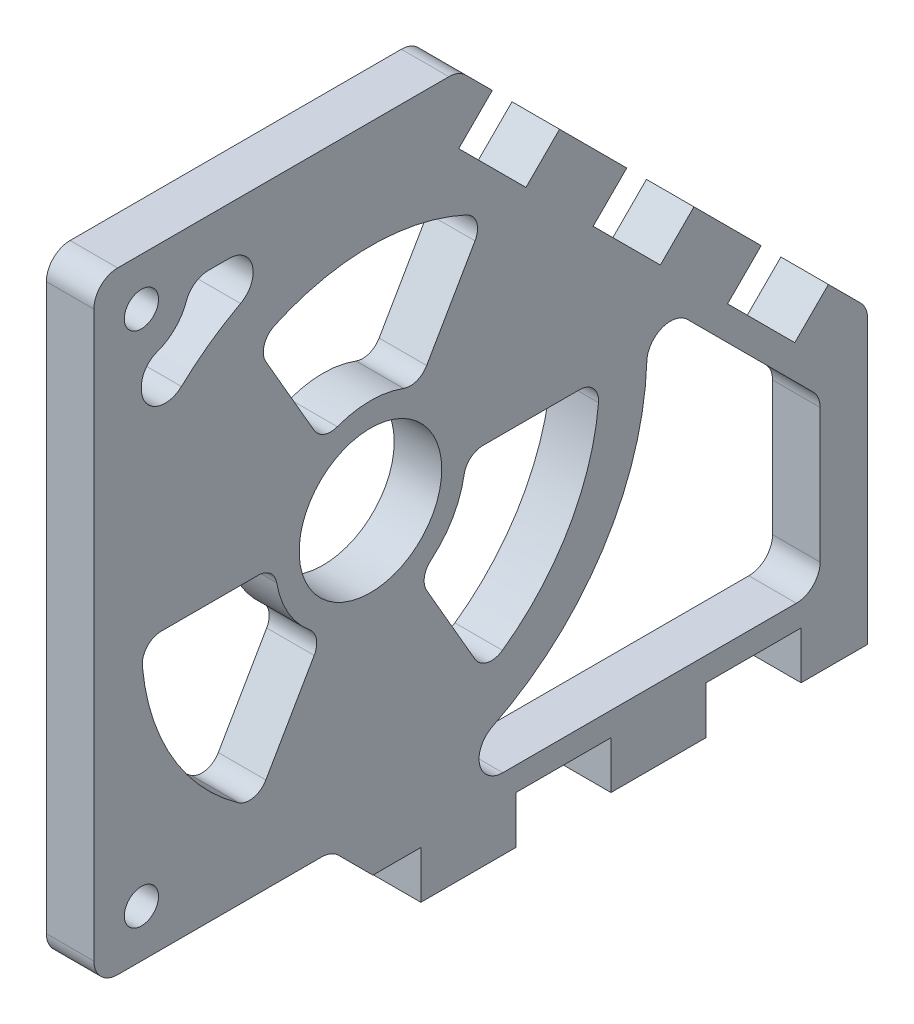
SolidWorks part; units mm, degrees
material "Custom Plastic"
ref_plane "Front Plane" through (0, 0, 0) normal (0, 0, 1) x (1, 0, 0)
ref_plane "Top Plane" through (0, 0, 0) normal (0, 1, 0) x (1, 0, 0)
ref_plane "Right Plane" through (0, 0, 0) normal (1, 0, 0) x (0, 0, -1)
sketch "Sketch2" plane through (0, 0, 0) normal (1, 0, 0) x (0, 0, -1)
  line L0 (0, 0) -> (0, 26.162) construction
  line L1 (0, 26.162) -> (0, 95.25) construction
  line L2 (-55.118, 95.25) -> (0, 95.25) construction
  line L3 (-61.468, 95.25) -> (-61.468, 26.162) construction
  line L4 (-61.468, 26.162) -> (0, 26.162) construction
  line L5 (-45.72, 0) -> (45.72, 0)
  line L6 (-67.818, 101.6) -> (-67.818, 19.812)
  line L7 (45.72, 7.9375) -> (-29.718, 7.9375)
  line L8 (45.72, 0) -> (52.07, 0)
  line L9 (-67.818, 19.812) -> (-45.72, 0)
  line L10 (-55.118, 101.6) -> (-19.0732, 101.6)
  line L11 (-61.468, 95.25) -> (-61.468, 101.6) construction
  line L12 (-61.468, 95.25) -> (-67.818, 95.25) construction
  line L13 (-61.468, 26.162) -> (-67.818, 26.162) construction
  line L14 (-61.468, 26.162) -> (-61.468, 19.812) construction
  line L15 (-55.118, 101.6) -> (-67.818, 101.6)
  line L16 (-61.468, 95.25) -> (-55.118, 95.25) construction
  line L17 (-36.068, 19.812) -> (-29.718, 13.462)
  line L18 (-55.118, 95.25) -> (-55.118, 101.6) construction
  line L19 (-67.818, 19.812) -> (-36.068, 19.812)
  line L20 (-29.718, 13.462) -> (-29.718, 7.9375)
  line L21 (52.07, 0) -> (52.07, 7.9375)
  line L22 (52.07, 7.9375) -> (45.72, 7.9375)
  line L23 (-29.718, 7.9375) -> (-24.1935, 7.9375)
  line L24 (-19.0732, 101.6) -> (52.07, 30.4568)
  line L25 (52.07, 30.4568) -> (52.07, 7.9375)
  circle A0 centre (-61.468, 95.25) radius 2.286
  circle A1 centre (-61.468, 26.162) radius 2.286
  point P0 (0, 0)
  point P1 (-61.468, 95.25)
  point P3 (-61.468, 26.162)
  dimension "D4" = 4.572
  dimension "D7" = 6.35
  dimension "D2" = 26.162
  dimension "D3" = 61.468
  dimension "D5" = 7.9375
  dimension "D6" = 91.44
  dimension "D8" = 6.35
  dimension "D9" = 31.75
  dimension "D10" = 45
  dimension "D11" = 95.25
  dimension "D12" = 6.35
  dimension "D13" = 69.85
extrude "Main" add sketch "Sketch2" along normal blind 6.35 contours L7 A1 A0 | L7 region at (0, 49.7959, 16.6078)
sketch "Sketch5" plane through (6.35, 0, 0) normal (1, 0, 0) x (0, 0, -1)
  line L0 (-36.83, 7.9375) -> (-36.83, 14.2875)
  line L1 (52.07, 7.9375) -> (-29.718, 7.9375) construction
  line L2 (-36.83, 14.2875) -> (-24.13, 14.2875)
  line L3 (-24.13, 14.2875) -> (-24.13, 7.9375)
  line L4 (-24.13, 7.9375) -> (-11.43, 7.9375) construction
  line L5 (-11.43, 7.9375) -> (-11.43, 14.2875)
  line L6 (-11.43, 14.2875) -> (1.27, 14.2875)
  line L7 (1.27, 14.2875) -> (1.27, 7.9375)
  line L8 (1.27, 7.9375) -> (13.97, 7.9375) construction
  line L9 (13.97, 7.9375) -> (13.97, 14.2875)
  line L10 (13.97, 14.2875) -> (26.67, 14.2875)
  line L11 (26.67, 14.2875) -> (26.67, 7.9375)
  line L12 (-19.0732, 101.6) -> (52.07, 30.4568) construction
  line L13 (-36.83, 7.9375) -> (-24.13, 7.9375)
  line L14 (-11.43, 7.9375) -> (1.27, 7.9375)
  line L15 (13.97, 7.9375) -> (26.67, 7.9375)
  line L16 (12.3577, 70.1691) -> (21.338, 61.1888) construction
  line L21 (16.8478, 56.6987) -> (21.338, 61.1888)
  line L22 (25.8281, 47.7185) -> (16.8478, 56.6987)
  line L23 (30.3182, 52.2086) -> (25.8281, 47.7185)
  line L24 (21.338, 61.1888) -> (30.3182, 52.2086)
  line L25 (-1.1127, 74.6592) -> (3.3775, 79.1494)
  line L26 (7.8676, 65.679) -> (-1.1127, 74.6592)
  line L27 (12.3577, 70.1691) -> (7.8676, 65.679)
  line L28 (3.3775, 79.1494) -> (12.3577, 70.1691)
  line L29 (-19.0732, 92.6197) -> (-14.5831, 97.1099)
  line L30 (-10.0929, 83.6395) -> (-19.0732, 92.6197)
  line L31 (-5.6028, 88.1296) -> (-10.0929, 83.6395)
  line L32 (-14.5831, 97.1099) -> (-5.6028, 88.1296)
  line L33 (-5.6028, 88.1296) -> (3.3775, 79.1494) construction
  line L35 (39.37, 7.9375) -> (39.37, 43.1568)
  line L36 (52.07, 7.9375) -> (-29.718, 7.9375) construction
  line L37 (39.37, 43.1568) -> (52.07, 43.1568)
  line L38 (52.07, 43.1568) -> (52.07, 7.9375)
  line L39 (52.07, 7.9375) -> (39.37, 7.9375)
  line L40 (26.67, 7.9375) -> (39.37, 7.9375) construction
  line L41 (52.07, 30.4568) -> (52.07, 7.9375) construction
  dimension "D5" = 6.35
  dimension "D1" = 6.35
  dimension "D2" = 12.7
extrude "Acrylic Joint" cut sketch "Sketch5" against normal through all
sketch "Sketch6" plane through (6.35, 0, 0) normal (1, 0, 0) x (0, 0, -1)
  line L0 (35.56, 7.9375) -> (35.56, 46.9668)
  line L1 (39.37, 7.9375) -> (26.67, 7.9375) construction
  line L2 (35.56, 46.9668) -> (39.37, 46.9668)
  line L3 (39.37, 43.1568) -> (39.37, 7.9375) construction
  line L4 (39.37, 46.9668) -> (39.37, 7.9375)
  line L5 (39.37, 7.9375) -> (35.56, 7.9375)
  line L6 (30.3182, 52.2086) -> (39.37, 43.1568) construction
  dimension "D2" = 3.81
extrude "Cut-Extrude1" cut sketch "Sketch6" against normal through all
fillet "Fillet4" radius 3.175 5 edges at (3.175, 101.6, 67.818) (3.175, 19.812, 67.818) (3.175, 19.812, 36.068) (3.175, 101.6, 19.0732) (3.175, 46.9668, -35.56)
sketch "Sketch7" plane through (6.35, 0, 0) normal (1, 0, 0) x (0, 0, -1)
  line L0 (-61.468, 95.25) -> (-26.1936, 95.25) construction
  line L1 (-26.1936, 95.25) -> (29.21, 39.8464) construction
  line L2 (29.21, 39.8464) -> (29.21, 17.4625) construction
  line L3 (29.21, 17.4625) -> (-24.7382, 17.4625) construction
  line L4 (-24.7382, 17.4625) -> (-33.4377, 26.162) construction
  line L5 (-33.4377, 26.162) -> (-61.468, 26.162) construction
  line L6 (-61.468, 26.162) -> (-61.468, 95.25) construction
  line L7 (-35.1381, 18.8821) -> (-30.5435, 14.2875) construction
  line L8 (-1.1127, 74.6592) -> (7.8676, 65.679) construction
  line L9 (1.27, 14.2875) -> (-11.43, 14.2875) construction
  line L10 (-64.643, 19.812) -> (-37.3831, 19.812) construction
  line L11 (-67.818, 98.425) -> (-67.818, 22.987) construction
  line L12 (-64.643, 101.6) -> (-20.3883, 101.6) construction
  line L13 (-46.1687, 83.1519) -> (-30.8693, 56.6527) construction
  line L14 (-30.8693, 56.6527) -> (-15.57, 83.1519) construction
  line L15 (-30.8693, 56.6527) -> (-0.2706, 56.6527) construction
  line L16 (-30.8693, 56.6527) -> (-15.57, 30.1535) construction
  line L17 (-30.8693, 56.6527) -> (-46.1687, 30.1535) construction
  line L18 (-30.8693, 56.6527) -> (-61.468, 56.6527) construction
  line L19 (-61.468, 56.6527) -> (-46.1687, 83.1519) construction
  line L20 (-46.1687, 83.1519) -> (-15.57, 83.1519) construction
  line L21 (-15.57, 83.1519) -> (-0.2706, 56.6527) construction
  line L22 (-0.2706, 56.6527) -> (-15.57, 30.1535) construction
  line L23 (-15.57, 30.1535) -> (-46.1687, 30.1535) construction
  line L24 (-46.1687, 30.1535) -> (-61.468, 56.6527) construction
  line L25 (35.56, 45.6517) -> (35.56, 7.9375) construction
  line L26 (-46.1687, 83.1519) -> (-37.2193, 67.6512)
  line L27 (-24.5193, 67.6512) -> (-15.57, 83.1519)
  line L28 (-18.1693, 56.6527) -> (-0.2706, 56.6527)
  line L29 (-15.57, 30.1535) -> (-24.5193, 45.6542)
  line L30 (-46.1687, 30.1535) -> (-37.2193, 45.6542)
  line L31 (-43.5693, 56.6527) -> (-61.468, 56.6527)
  arc A0 (-46.1687, 30.1535) -> (-61.468, 56.6527) centre (-30.8693, 56.6527) cw
  arc A1 (-46.1687, 83.1519) -> (-61.468, 56.6527) centre (-30.8693, 56.6527) ccw construction
  arc A2 (-46.1687, 30.1535) -> (-15.57, 30.1535) centre (-30.8693, 56.6527) ccw construction
  arc A3 (-0.2706, 56.6527) -> (-15.57, 83.1519) centre (-30.8693, 56.6527) ccw construction
  arc A4 (-46.1687, 83.1519) -> (-15.57, 83.1519) centre (-30.8693, 56.6527) cw
  arc A5 (-15.57, 30.1535) -> (-0.2706, 56.6527) centre (-30.8693, 56.6527) ccw
  circle A6 centre (-30.8693, 56.6527) radius 12.7 construction
  circle A7 centre (-30.8693, 56.6527) radius 9.525
  arc A8 (-24.5193, 67.6512) -> (-37.2193, 67.6512) centre (-30.8693, 56.6527) ccw
  arc A9 (-43.5693, 56.6527) -> (-37.2193, 45.6542) centre (-30.8693, 56.6527) ccw
  arc A10 (-24.5193, 45.6542) -> (-18.1693, 56.6527) centre (-30.8693, 56.6527) ccw
  dimension "D8" = 19.05
  dimension "D9" = 3.175
  dimension "D1" = 6.35
  dimension "D2" = 3.175
  dimension "D3" = 3.175
  dimension "D4" = 6.35
  dimension "D5" = 6.35
  dimension "D6" = 6.35
  dimension "D7" = 6.35
extrude "Cut-Extrude2" cut sketch "Sketch7" against normal through all
fillet "Fillet5" radius 2.54 12 edges at (3.175, 56.6527, 0.2706) (3.175, 83.1519, 15.57) (3.175, 45.6542, 37.2193) (3.175, 56.6527, 43.5693) (3.175, 30.1535, 46.1687) (3.175, 30.1535, 15.57) (3.175, 67.6512, 24.5193) (3.175, 67.6512, 37.2193) (3.175, 45.6542, 24.5193) (3.175, 56.6527, 18.1693) (3.175, 56.6527, 61.468) (3.175, 83.1519, 46.1687)
sketch "Sketch8" plane through (6.35, 0, 0) normal (1, 0, 0) x (0, 0, -1)
  line L0 (-33.7185, 17.4625) -> (29.21, 17.4625) construction
  line L1 (29.21, 17.4625) -> (29.21, 39.8464) construction
  line L2 (29.21, 39.8464) -> (5.4118, 63.6447) construction
  line L3 (16.8478, 56.6987) -> (25.8281, 47.7185) construction
  line L4 (35.56, 45.6517) -> (35.56, 7.9375) construction
  line L5 (1.27, 14.2875) -> (-11.43, 14.2875) construction
  line L6 (5.4118, 63.6447) -> (29.21, 39.8464)
  line L7 (29.21, 39.8464) -> (29.21, 17.4625)
  line L8 (29.21, 17.4625) -> (-13.1827, 17.4625)
  line L9 (-35.1381, 18.8821) -> (-30.5435, 14.2875) construction
  line L10 (-25.7744, 95.25) -> (-61.468, 95.25) construction
  line L11 (-61.468, 95.25) -> (-61.468, 77.3632) construction
  line L12 (-67.818, 98.425) -> (-67.818, 22.987) construction
  line L13 (-64.643, 101.6) -> (-20.3883, 101.6) construction
  line L14 (-61.468, 88.9) -> (-61.468, 77.3632)
  line L15 (-55.118, 95.25) -> (-49.7153, 95.25)
  circle A0 centre (-30.8693, 56.6527) radius 36.9487 construction
  arc A1 (-18.0316, 84.4281) -> (-43.707, 84.4281) centre (-30.8693, 56.6527) ccw construction
  arc A2 (-14.5823, 23.4874) -> (-13.1827, 17.4625) centre (-13.1827, 20.6375) ccw
  arc A3 (-14.5823, 23.4874) -> (5.4118, 63.6447) centre (-30.8693, 56.6527) ccw
  arc A4 (-49.7153, 95.25) -> (-48.224, 89.272) centre (-49.7153, 92.075) cw
  arc A5 (-55.118, 95.25) -> (-61.468, 88.9) centre (-61.468, 95.25) cw
  arc A6 (-61.468, 77.3632) -> (-48.224, 89.272) centre (-30.8693, 56.6527) cw
  point P16 (35.56, 26.7946)
  dimension "D1" = 6.35
  dimension "D5" = 3.175
  dimension "D8" = 6.35
  dimension "D2" = 3.175
  dimension "D3" = 6.35
  dimension "D4" = 3.175
  dimension "D6" = 6.35
  dimension "D7" = 6.35
extrude "Cut-Extrude3" cut sketch "Sketch8" against normal through all
fillet "Fillet6" radius 3.175 6 edges at (3.175, 17.4625, -29.21) (3.175, 39.8464, -29.21) (3.175, 63.6447, -5.4118) (3.175, 77.3632, 61.468) (3.175, 88.9, 61.468) (3.175, 95.25, 55.118)
